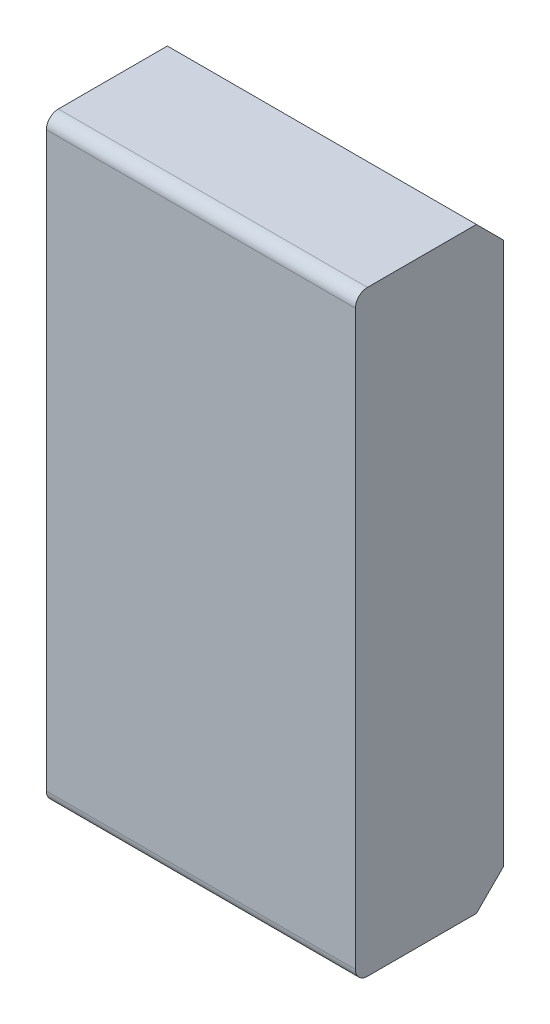
SolidWorks part; units mm, degrees
ref_plane "Front Plane" through (0, 0, 0) normal (1, 0, 0) x (0, 1, 0)
ref_plane "Top Plane" through (0, 0, 0) normal (0, 0, 1) x (0, 1, 0)
ref_plane "Right Plane" through (0, 0, 0) normal (0, 1, 0) x (-1, 0, 0)
sketch "Sketch1" plane through (0, 0, 0) normal (1, 0, 0) x (0, 1, 0)
  line L12 (-98.46, -46.9834) -> (-89.4834, -55.96)
  line L13 (-89.4834, -55.96) -> (89.4834, -55.96)
  line L14 (89.4834, -55.96) -> (98.46, -46.9834)
  line L15 (98.46, -46.9834) -> (98.46, -11)
  line L16 (94.5, -7.04) -> (-94.5, -7.04)
  line L17 (-98.46, -11) -> (-98.46, -46.9834)
  line L18 (-98.46, -46.9834) -> (-89.4834, -55.96)
  line L19 (-89.4834, -55.96) -> (89.4834, -55.96)
  line L20 (89.4834, -55.96) -> (98.46, -46.9834)
  line L21 (98.46, -46.9834) -> (98.46, -11)
  line L22 (94.5, -7.04) -> (-94.5, -7.04)
  line L23 (-98.46, -11) -> (-98.46, -46.9834)
  arc A4 (98.46, -11) -> (94.5, -7.04) centre (94.5, -11) ccw
  arc A5 (-94.5, -7.04) -> (-98.46, -11) centre (-94.5, -11) ccw
  arc A6 (98.46, -11) -> (94.5, -7.04) centre (94.5, -11) ccw
  arc A7 (-94.5, -7.04) -> (-98.46, -11) centre (-94.5, -11) ccw
  dimension "D1" = 0.04
extrude "Boss-Extrude1" add sketch "Sketch1" along normal up to surface (102 mm away) contours L18 L19 L20 L21 A6 L22 A7 L23
sketch "Sketch2" plane through (102, 0, 0) normal (1, 0, 0) x (0, 1, 0)
  line L0 (0, -55.96) -> (0, -7.04)
  line L1 (89.4834, -55.96) -> (-89.4834, -55.96) construction
  line L2 (-94.5, -7.04) -> (94.5, -7.04) construction
  line L3 (0, -31.5) -> (28.8544, -31.5)
